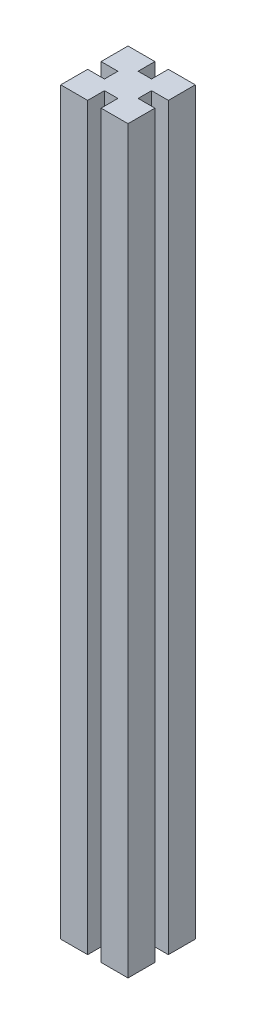
SolidWorks part; units mm, degrees
ref_plane "Front Plane" through (0, 0, 0) normal (0, 0, 1) x (1, 0, 0)
ref_plane "Top Plane" through (0, 0, 0) normal (0, 1, 0) x (1, 0, 0)
ref_plane "Right Plane" through (0, 0, 0) normal (1, 0, 0) x (0, 0, -1)
sketch "Sketch1" plane through (0, 0, 0) normal (0, 1, 0) x (1, 0, 0)
  line L0 (0, 12.5) -> (0, -25) construction
  line L1 (-25, 25) -> (-5, 25)
  line L2 (-25, 25) -> (-25, 5)
  line L3 (-25, -25) -> (-5, -25)
  line L4 (25, 25) -> (25, 5)
  line L5 (-25, 25) -> (25, -25) construction
  line L6 (-25, -25) -> (25, 25) construction
  line L7 (-25, 0) -> (12.5, 0) construction
  line L8 (-5, 25) -> (-5, 12.5)
  line L9 (-5, 12.5) -> (5, 12.5)
  line L10 (-5, -12.5) -> (5, -12.5)
  line L11 (-5, -25) -> (-5, -12.5)
  line L12 (-25, 5) -> (-12.5, 5)
  line L13 (-12.5, 5) -> (-12.5, -5)
  line L14 (12.5, 5) -> (12.5, -5)
  line L15 (25, 5) -> (12.5, 5)
  line L16 (25, -5) -> (12.5, -5)
  line L17 (-25, -5) -> (-12.5, -5)
  line L18 (5, -25) -> (5, -12.5)
  line L19 (5, 25) -> (5, 12.5)
  line L20 (5, 25) -> (25, 25)
  line L21 (25, -5) -> (25, -25)
  line L22 (5, -25) -> (25, -25)
  line L23 (-25, -5) -> (-25, -25)
  point P0 (0, 0)
  point P24 (12.5, 0)
  point P25 (-12.5, 0)
  point P28 (0, -12.5)
  point P29 (0, 12.5)
  dimension "D1" = 50
  dimension "D2" = 10
  dimension "D3" = 12.5
  dimension "D4" = 50
extrude "Boss-Extrude1" add sketch "Sketch1" along normal blind 550
extrude "Boss-Extrude2" add sketch "Sketch1<2>" along normal blind 10
sketch "Sketch1<2>" plane through (0, 0, 0) normal (0, 1, 0) x (1, 0, 0) same geometry as "Sketch1"
